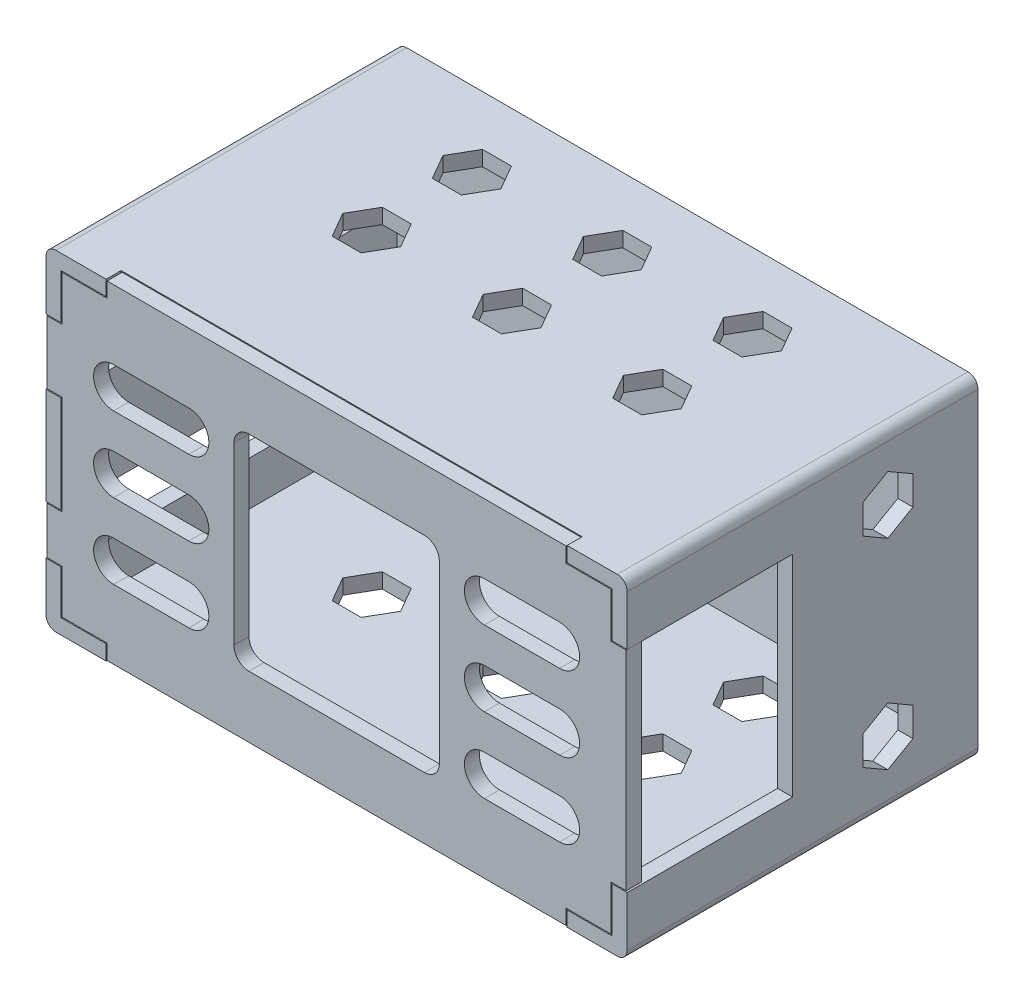
SolidWorks part; units mm, degrees
ref_plane "Front Plane" through (0, 0, 0) normal (0, 0, 1) x (1, 0, 0)
ref_plane "Top Plane" through (0, 0, 0) normal (0, 1, 0) x (1, 0, 0)
ref_plane "Right Plane" through (0, 0, 0) normal (1, 0, 0) x (0, 0, -1)
sketch "Sketch1" plane through (0, 0, 0) normal (0, 0, 1) x (1, 0, 0)
  line L0 (-58, -33) -> (-58, 33)
  line L1 (-55, -30) -> (55, -30)
  line L2 (-55, -30) -> (-55, 30)
  line L3 (-55, 30) -> (55, 30)
  line L4 (55, -30) -> (55, 30)
  line L5 (-55, -30) -> (55, 30) construction
  line L6 (-55, 30) -> (55, -30) construction
  line L7 (-58, 33) -> (58, 33)
  line L8 (58, -33) -> (58, 33)
  line L9 (-58, -33) -> (58, -33)
  point P0 (0, 0)
  dimension "D1" = 60
  dimension "125" = 110
  dimension "D3" = 3
extrude "Boss-Extrude1" add sketch "Sketch1" along normal blind 70
extrude "Boss-Extrude2" add sketch "Sketch1<2>" along normal blind 3 contours L1 L4 L3 L2 region at (0, 0, 0)
sketch "Sketch1<2>" plane through (0, 0, 0) normal (0, 0, 1) x (1, 0, 0) same geometry as "Sketch1"
sketch "Sketch2" plane through (-58, 0, 0) normal (-1, 0, 0) x (0, 0, 1)
  line L0 (70, 33) -> (70, -33) construction
  line L1 (70, -11.4) -> (5, -11.4)
  line L2 (70, -11.4) -> (70, -21.2)
  line L3 (70, -21.2) -> (5, -21.2)
  line L4 (5, -11.4) -> (5, -21.2)
  line L5 (0, 33) -> (0, -33) construction
  line L6 (70, 21) -> (5, 21)
  line L7 (70, 21) -> (70, 8)
  line L8 (70, 8) -> (5, 8)
  line L9 (5, 21) -> (5, 8)
  line L11 (70, 33) -> (0, 33) construction
  dimension "D1" = 5
  dimension "D2" = 13
  dimension "D3" = 9.8
  dimension "D4" = 19.4
  dimension "D5" = 12
extrude "Cut-Extrude1" cut sketch "Sketch2" against normal up to next
sketch "Sketch3" plane through (0, -33, 0) normal (0, -1, 0) x (1, 0, 0)
  line L0 (-58, 35) -> (58, 35) construction
  line L1 (-58, 70) -> (-58, 0) construction
  line L2 (58, 70) -> (58, 0) construction
  line L3 (-58, 15) -> (58, 15) construction
  line L9 (-25.1132, 40) -> (-30.8868, 40)
  line L14 (-30.8868, 40) -> (-33.7735, 35)
  line L15 (-33.7735, 35) -> (-30.8868, 30)
  line L20 (-30.8868, 30) -> (-25.1132, 30)
  line L21 (-25.1132, 30) -> (-22.2265, 35)
  line L22 (-58, 0) -> (58, 0) construction
  line L27 (-22.2265, 35) -> (-25.1132, 40)
  line L28 (2.8868, 40) -> (-2.8868, 40)
  line L33 (-2.8868, 40) -> (-5.7735, 35)
  line L34 (-5.7735, 35) -> (-2.8868, 30)
  line L39 (-2.8868, 30) -> (2.8868, 30)
  line L40 (2.8868, 30) -> (5.7735, 35)
  line L41 (5.7735, 35) -> (2.8868, 40)
  line L42 (30.8868, 40) -> (25.1132, 40)
  line L43 (25.1132, 40) -> (22.2265, 35)
  line L44 (22.2265, 35) -> (25.1132, 30)
  line L45 (25.1132, 30) -> (30.8868, 30)
  line L46 (30.8868, 30) -> (33.7735, 35)
  line L47 (33.7735, 35) -> (30.8868, 40)
  line L48 (30.8868, 20) -> (25.1132, 20)
  line L49 (25.1132, 20) -> (22.2265, 15)
  line L50 (22.2265, 15) -> (25.1132, 10)
  line L51 (25.1132, 10) -> (30.8868, 10)
  line L52 (30.8868, 10) -> (33.7735, 15)
  line L53 (33.7735, 15) -> (30.8868, 20)
  line L54 (2.8868, 20) -> (-2.8868, 20)
  line L55 (-2.8868, 20) -> (-5.7735, 15)
  line L56 (-5.7735, 15) -> (-2.8868, 10)
  line L57 (-2.8868, 10) -> (2.8868, 10)
  line L58 (2.8868, 10) -> (5.7735, 15)
  line L59 (5.7735, 15) -> (2.8868, 20)
  line L60 (-25.1132, 20) -> (-30.8868, 20)
  line L61 (-30.8868, 20) -> (-33.7735, 15)
  line L62 (-33.7735, 15) -> (-30.8868, 10)
  line L63 (-30.8868, 10) -> (-25.1132, 10)
  line L64 (-25.1132, 10) -> (-22.2265, 15)
  line L65 (-22.2265, 15) -> (-25.1132, 20)
  circle A0 centre (-28, 35) radius 5 construction
  circle A1 centre (0, 35) radius 5 construction
  circle A2 centre (28, 35) radius 5 construction
  circle A3 centre (28, 15) radius 5 construction
  circle A4 centre (0, 15) radius 5 construction
  circle A5 centre (-28, 15) radius 5 construction
  point P6 (-28, 35)
  point P11 (0, 35)
  point P16 (28, 35)
  point P23 (-28, 15)
  point P28 (0, 15)
  point P33 (28, 15)
  dimension "D5" = 10
  dimension "D1" = 28
  dimension "D2" = 28
  dimension "D3" = 15
  dimension "D4" = 20
extrude "Cut-Extrude2" cut sketch "Sketch3" against normal through all
sketch "Sketch4" plane through (58, 0, 0) normal (1, 0, 0) x (0, 0, -1)
  line L0 (-35, 33) -> (-35, -33) construction
  line L1 (-70, 33) -> (0, 33) construction
  line L2 (-40, -33) -> (-30, -33) construction
  line L3 (-18, 33) -> (-18, -33) construction
  line L4 (-20, -33) -> (-10, -33) construction
  line L5 (0, -33) -> (0, 33) construction
  line L7 (-40.7735, 20) -> (-37.8868, 15) construction
  line L8 (-37.8868, 15) -> (-32.1132, 15) construction
  line L9 (-32.1132, 15) -> (-29.2265, 20) construction
  line L10 (-29.2265, 20) -> (-32.1132, 25) construction
  line L11 (-32.1132, 25) -> (-37.8868, 25) construction
  line L12 (-37.8868, 25) -> (-40.7735, 20) construction
  line L13 (-18, 25.7735) -> (-23, 22.8868)
  line L14 (-23, 22.8868) -> (-23, 17.1132)
  line L15 (-23, 17.1132) -> (-18, 14.2265)
  line L16 (-18, 14.2265) -> (-13, 17.1132)
  line L17 (-13, 17.1132) -> (-13, 22.8868)
  line L18 (-13, 22.8868) -> (-18, 25.7735)
  line L19 (-18, -14.2265) -> (-23, -17.1132)
  line L20 (-23, -17.1132) -> (-23, -22.8868)
  line L21 (-23, -22.8868) -> (-18, -25.7735)
  line L22 (-18, -25.7735) -> (-13, -22.8868)
  line L23 (-13, -22.8868) -> (-13, -17.1132)
  line L24 (-13, -17.1132) -> (-18, -14.2265)
  line L25 (-40.7735, -20) -> (-37.8868, -25) construction
  line L26 (-37.8868, -25) -> (-32.1132, -25) construction
  line L27 (-32.1132, -25) -> (-29.2265, -20) construction
  line L28 (-29.2265, -20) -> (-32.1132, -15) construction
  line L29 (-32.1132, -15) -> (-37.8868, -15) construction
  line L30 (-37.8868, -15) -> (-40.7735, -20) construction
  circle A0 centre (-35, 20) radius 5 construction
  circle A1 centre (-18, 20) radius 5 construction
  circle A2 centre (-18, -20) radius 5 construction
  circle A3 centre (-35, -20) radius 5 construction
  dimension "D3" = 10
  dimension "D1" = 18
  dimension "D2" = 35
  dimension "D4" = 20
  dimension "D5" = 20
extrude "Cut-Extrude3" cut sketch "Sketch4" against normal up to next
sketch "Sketch5" plane through (0, 0, 70) normal (0, 0, 1) x (1, 0, 0)
  line L0 (58, 33) -> (-58, 33) construction
  line L1 (-46, 33) -> (46, 33)
  line L2 (-46, 33) -> (-46, 30)
  line L3 (-46, 30) -> (46, 30)
  line L4 (46, 33) -> (46, 30)
  line L5 (-55, 30) -> (55, 30) construction
  line L6 (58, -33) -> (58, 33) construction
  line L7 (-58, 33) -> (-58, 21) construction
  line L8 (-55, -30) -> (55, -30) construction
  line L9 (-46, -30) -> (46, -30)
  line L10 (-46, -30) -> (-46, -33)
  line L11 (-46, -33) -> (46, -33)
  line L12 (46, -30) -> (46, -33)
  line L13 (-58, -33) -> (58, -33) construction
  line L14 (-58, -21.2) -> (-58, -33) construction
  line L15 (55, -30) -> (55, 30) construction
  line L16 (55, 21) -> (58, 21)
  line L17 (55, 21) -> (55, -21)
  line L18 (55, -21) -> (58, -21)
  line L19 (58, 21) -> (58, -21)
  point P28 (55, 0)
  dimension "D1" = 12
  dimension "D2" = 12
  dimension "D3" = 12
  dimension "D4" = 12
  dimension "D5" = 12
extrude "Cut-Extrude4" cut sketch "Sketch5" against normal blind 3
sketch "Sketch6" plane through (0, 0, 67) normal (0, 0, 1) x (1, 0, 0)
  line L0 (-55, 21) -> (-58, 21) construction
  line L1 (-58, 21) -> (-58, 8) construction
  line L2 (-58, 8) -> (-55, 8) construction
  line L4 (-55, -11.4) -> (-58, -11.4) construction
  line L5 (-58, -11.4) -> (-58, -21.2) construction
  line L6 (-58, -21.2) -> (-55, -21.2) construction
  line L8 (-46, -30) -> (-46, -33) construction
  line L9 (-46, -33) -> (46, -33) construction
  line L10 (46, -33) -> (46, -30) construction
  line L13 (55, -21) -> (58, -21) construction
  line L14 (58, -21) -> (58, 21) construction
  line L15 (58, 21) -> (55, 21) construction
  line L16 (-46, 33) -> (-46, 30) construction
  line L18 (46, 30) -> (46, 33) construction
  line L19 (46, 33) -> (-46, 33) construction
  line L20 (-55, -30) -> (55, -30) construction
  line L21 (55, -30) -> (55, 30) construction
  line L22 (55, 30) -> (-55, 30) construction
  line L23 (-55, 30) -> (-55, -30) construction
  line L24 (-55, 21) -> (-58, 21)
  line L25 (-58, 21) -> (-58, 8)
  line L26 (-58, 8) -> (-55, 8)
  line L28 (-55, -11.4) -> (-58, -11.4)
  line L29 (-58, -11.4) -> (-58, -21.2)
  line L30 (-58, -21.2) -> (-55, -21.2)
  line L32 (-46, -30) -> (-46, -33)
  line L33 (-46, -33) -> (46, -33)
  line L34 (46, -33) -> (46, -30)
  line L37 (55, -21) -> (58, -21)
  line L38 (58, -21) -> (58, 21)
  line L39 (58, 21) -> (55, 21)
  line L40 (-46, 33) -> (-46, 30)
  line L42 (46, 30) -> (46, 33)
  line L43 (46, 33) -> (-46, 33)
  line L44 (-55, -30) -> (-46, -30)
  line L45 (55, -30) -> (55, -21)
  line L46 (55, 30) -> (46, 30)
  line L47 (-55, 30) -> (-55, 21)
  line L48 (-55, 8) -> (-55, -11.4)
  line L49 (-55, -21.2) -> (-55, -30)
  line L50 (46, -30) -> (55, -30)
  line L51 (55, 21) -> (55, 30)
  line L52 (-46, 30) -> (-55, 30)
  line L53 (54.8, 29.8) -> (45.8, 29.8)
  line L54 (45.8, 29.8) -> (45.8, 32.8)
  line L55 (45.8, 32.8) -> (-45.8, 32.8)
  line L56 (-45.8, 32.8) -> (-45.8, 29.8)
  line L57 (-45.8, 29.8) -> (-54.8, 29.8)
  line L58 (-54.8, 29.8) -> (-54.8, 20.8)
  line L59 (-54.8, 20.8) -> (-57.8, 20.8)
  line L60 (-57.8, 20.8) -> (-57.8, 8.2)
  line L61 (-57.8, 8.2) -> (-54.8, 8.2)
  line L62 (-54.8, 8.2) -> (-54.8, -11.6)
  line L63 (-54.8, -11.6) -> (-57.8, -11.6)
  line L64 (-57.8, -11.6) -> (-57.8, -21)
  line L65 (-57.8, -21) -> (-54.8, -21)
  line L66 (-54.8, -21) -> (-54.8, -29.8)
  line L67 (-54.8, -29.8) -> (-45.8, -29.8)
  line L68 (-45.8, -29.8) -> (-45.8, -32.8)
  line L69 (-45.8, -32.8) -> (45.8, -32.8)
  line L70 (45.8, -32.8) -> (45.8, -29.8)
  line L71 (45.8, -29.8) -> (54.8, -29.8)
  line L72 (54.8, -29.8) -> (54.8, -20.8)
  line L73 (54.8, -20.8) -> (57.8, -20.8)
  line L74 (57.8, -20.8) -> (57.8, 20.8)
  line L75 (57.8, 20.8) -> (54.8, 20.8)
  line L76 (54.8, 20.8) -> (54.8, 29.8)
  line M51 (55, 21) -> (55, -21)
  dimension "D1" = 0.2
extrude "Boss-Extrude3" add sketch "Sketch6" along normal blind 3 separate body contours L75 L76 L53 L54 L55 L56 L57 L58 L59 L60 L61 L62 L63 L64 L65 L66 L67 L68 L69 L70 L71 L72 L73 M51 | L74 L75 L73 M51 region at (-0.4554, 0.0124, 67) region at (56.4, 0, 67)
sketch "Sketch7" plane through (0, 0, 70) normal (0, 0, 1) x (1, 0, 0)
  line L1 (-32.5, 24) -> (32.5, 24)
  line L2 (-32.5, 24) -> (-32.5, 18)
  line L3 (-32.5, 18) -> (32.5, 18)
  line L4 (32.5, 24) -> (32.5, 18)
  line L5 (-32.5, 10) -> (32.5, 10)
  line L6 (-32.5, 10) -> (-32.5, 4)
  line L7 (-32.5, 4) -> (32.5, 4)
  line L8 (32.5, 10) -> (32.5, 4)
  line L9 (-32.5, -4) -> (32.5, -4)
  line L10 (-32.5, -4) -> (-32.5, -10)
  line L11 (-32.5, -10) -> (32.5, -10)
  line L12 (32.5, -4) -> (32.5, -10)
  line L13 (-32.5, -18) -> (32.5, -18)
  line L14 (-32.5, -18) -> (-32.5, -24)
  line L15 (-32.5, -24) -> (32.5, -24)
  line L16 (32.5, -18) -> (32.5, -24)
  point P16 (0, -18)
  point P17 (0, -4)
  point P19 (0, 10)
  point P20 (0, 24)
  dimension "D1" = 6
  dimension "D2" = 65
  dimension "D3" = 4
  dimension "D4" = 4
  dimension "D5" = 8
  dimension "D6" = 8
extrude "Cut-Extrude5" [suppressed] cut sketch "Sketch7" against normal up to next
sketch "Sketch8" plane through (0, 0, 67) normal (0, 0, 1) x (1, 0, 0)
  line L4 (55, 21) -> (55, -21)
  line L5 (55, -21) -> (58, -21)
  line L6 (58, -21) -> (58, 21)
  line L7 (58, 21) -> (55, 21)
  line L8 (55, 21) -> (55, -21)
  line L9 (55, -21) -> (58, -21)
  line L10 (58, -21) -> (58, 21)
  line L11 (58, 21) -> (55, 21)
  dimension "D1" = 0
extrude "Cut-Extrude6" cut sketch "Sketch8" against normal blind 30
chamfer "Chamfer1" [suppressed] distance 2 angle 45
fillet "Fillet1" radius 2 4 edges at (58, 33, 35) (-58, 33, 35) (58, -33, 35) (-58, -33, 35)
sketch "Sketch9" plane through (0, 0, 70) normal (0, 0, 1) x (1, 0, 0)
  line L1 (-20.5, -20.5) -> (20.5, -20.5)
  line L2 (-20.5, -20.5) -> (-20.5, 20.5)
  line L3 (-20.5, 20.5) -> (20.5, 20.5)
  line L4 (20.5, -20.5) -> (20.5, 20.5)
  line L5 (-20.5, -20.5) -> (20.5, 20.5) construction
  line L6 (-20.5, 20.5) -> (20.5, -20.5) construction
  point P0 (0, 0)
  dimension "D1" = 41
extrude "Cut-Extrude7" cut sketch "Sketch9" against normal up to surface (3 mm away) up to face at (-9.3833, -0.3, 67)
fillet "Fillet2" radius 3 4 edges at (-20.5, -20.5, 68.5) (20.5, -20.5, 68.5) (20.5, 20.5, 68.5) (-20.5, 20.5, 68.5)
sketch "Sketch10" plane through (0, 0, 70) normal (0, 0, 1) x (1, 0, 0)
  line L0 (-44.5, 15) -> (-29.5, 15) construction
  line L1 (-44.5, 19) -> (-29.5, 19)
  line L2 (-44.5, 11) -> (-29.5, 11)
  line L3 (-44.5, 0) -> (-29.5, 0) construction
  line L4 (-44.5, 4) -> (-29.5, 4)
  line L5 (-44.5, -4) -> (-29.5, -4)
  line L6 (-44.5, -15) -> (-29.5, -15) construction
  line L7 (-44.5, -11) -> (-29.5, -11)
  line L8 (-44.5, -19) -> (-29.5, -19)
  line L9 (-20.5, 17.5) -> (-20.5, -17.5) construction
  line L10 (0, 41.2202) -> (0, -41.2202) construction
  line L11 (44.5, 15) -> (29.5, 15) construction
  line L12 (44.5, 19) -> (29.5, 19)
  line L13 (44.5, 11) -> (29.5, 11)
  line L14 (44.5, 0) -> (29.5, 0) construction
  line L15 (44.5, 4) -> (29.5, 4)
  line L16 (44.5, -4) -> (29.5, -4)
  line L17 (44.5, -15) -> (29.5, -15) construction
  line L18 (44.5, -11) -> (29.5, -11)
  line L19 (44.5, -19) -> (29.5, -19)
  arc A0 (-44.5, 19) -> (-44.5, 11) centre (-44.5, 15) ccw
  arc A1 (-29.5, 11) -> (-29.5, 19) centre (-29.5, 15) ccw
  arc A2 (-44.5, 4) -> (-44.5, -4) centre (-44.5, 0) ccw
  arc A3 (-29.5, -4) -> (-29.5, 4) centre (-29.5, 0) ccw
  arc A4 (-44.5, -11) -> (-44.5, -19) centre (-44.5, -15) ccw
  arc A5 (-29.5, -19) -> (-29.5, -11) centre (-29.5, -15) ccw
  arc A6 (44.5, 19) -> (44.5, 11) centre (44.5, 15) cw
  arc A7 (29.5, 11) -> (29.5, 19) centre (29.5, 15) cw
  arc A8 (44.5, 4) -> (44.5, -4) centre (44.5, 0) cw
  arc A9 (29.5, -4) -> (29.5, 4) centre (29.5, 0) cw
  arc A10 (44.5, -11) -> (44.5, -19) centre (44.5, -15) cw
  arc A11 (29.5, -19) -> (29.5, -11) centre (29.5, -15) cw
  point P2 (-37, 15)
  point P9 (-37, 0)
  point P16 (-37, -15)
  point P28 (37, 15)
  point P35 (37, 0)
  point P42 (37, -15)
  dimension "D4" = 4
  dimension "D1" = 15
  dimension "D2" = 15
  dimension "D3" = 15
  dimension "D5" = 9
extrude "Cut-Extrude8" cut sketch "Sketch10" against normal blind 10
